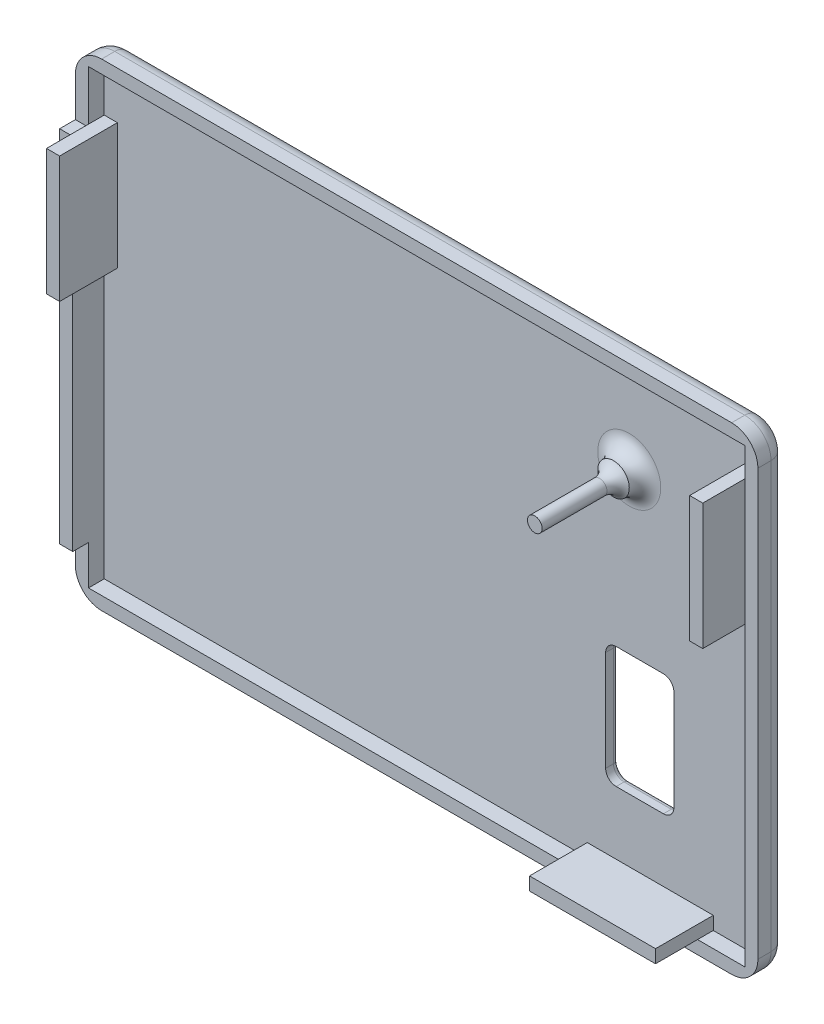
SolidWorks part; units mm, degrees
ref_plane "Front Plane" through (0, 0, 0) normal (0, 0, 1) x (1, 0, 0)
ref_plane "Top Plane" through (0, 0, 0) normal (0, 1, 0) x (1, 0, 0)
ref_plane "Right Plane" through (0, 0, 0) normal (1, 0, 0) x (0, 0, -1)
sketch "Sketch1" plane through (0, 0, 0) normal (0, 0, 1) x (1, 0, 0)
  line L1 (0, 0) -> (130, 0)
  line L2 (0, 0) -> (0, -91)
  line L3 (0, -91) -> (130, -91)
  line L4 (130, 0) -> (130, -91)
  dimension "D1" = 130
  dimension "D2" = 91
extrude "Boss-Extrude1" add sketch "Sketch1" along normal blind 2.5 contours L2 L1 L4 L3
sketch "Sketch2" plane through (0, 0, 2.5) normal (0, 0, 1) x (1, 0, 0)
  line L0 (0, 0) -> (130, 0) construction
  line L1 (0, 0) -> (130, 0)
  line L2 (0, 0) -> (0, -2.5)
  line L3 (0, -2.5) -> (130, -2.5)
  line L4 (130, 0) -> (130, -2.5)
  line L5 (0, 0) -> (0, -91) construction
  dimension "D1" = 2.5
  dimension "D2" = 130
sketch "Sketch3" plane through (0, 0, 2.5) normal (0, 0, 1) x (1, 0, 0)
  line L0 (0, -91) -> (130, -91) construction
  line L1 (0, -88.5) -> (130, -88.5)
  line L2 (0, -88.5) -> (0, -91)
  line L3 (0, -91) -> (130, -91)
  line L4 (130, -88.5) -> (130, -91)
  line L5 (130, 0) -> (130, -91) construction
  dimension "D1" = 130
  dimension "D2" = 2.5
sketch "Sketch4" plane through (0, 0, 2.5) normal (0, 0, 1) x (1, 0, 0)
  line L0 (0, -2.5) -> (130, -2.5) construction
  line L1 (127.5, -2.5) -> (130, -2.5)
  line L2 (127.5, -2.5) -> (127.5, -88.5)
  line L3 (127.5, -88.5) -> (130, -88.5)
  line L4 (130, -2.5) -> (130, -88.5)
  line L5 (0, -88.5) -> (130, -88.5) construction
  line L6 (130, 0) -> (130, -91) construction
  dimension "D1" = 2.5
sketch "Sketch5" plane through (0, 0, 2.5) normal (0, 0, 1) x (1, 0, 0)
  line L0 (0, 0) -> (0, -91) construction
  line L1 (0, -2.5) -> (2.5, -2.5)
  line L2 (0, -2.5) -> (0, -88.5)
  line L3 (0, -88.5) -> (2.5, -88.5)
  line L4 (2.5, -2.5) -> (2.5, -88.5)
  line L7 (0, -2.5) -> (130, -2.5) construction
  dimension "D1" = 2.5
  dimension "D2" = 86
extrude "Boss-Extrude2" add sketch "Sketch3" along normal blind 3
extrude "Boss-Extrude3" add sketch "Sketch2" along normal blind 3
extrude "Boss-Extrude4" add sketch "Sketch4" along normal blind 3
extrude "Boss-Extrude5" add sketch "Sketch5" along normal blind 3
fillet "Fillet2" radius 5 1 edges at (130, -91, 2.75)
fillet "Fillet3" radius 5 1 edges at (130, 0, 2.75)
fillet "Fillet4" radius 5 1 edges at (0, 0, 2.75)
fillet "Fillet5" radius 5 1 edges at (0, -91, 2.75)
sketch "Sketch7" plane through (0, 0, 5.5) normal (0, 0, 1) x (1, 0, 0)
  line L0 (0, -5) -> (0, -86) construction
  line L1 (0, -12.5) -> (2.5, -12.5)
  line L2 (0, -12.5) -> (0, -81)
  line L3 (0, -81) -> (2.5, -81)
  line L4 (2.5, -12.5) -> (2.5, -81)
  line L5 (2.5, -88.5) -> (2.5, -2.5) construction
  line L6 (127.5, -88.5) -> (2.5, -88.5) construction
  dimension "D1" = 68.5
  dimension "D2" = 7.5
extrude "Boss-Extrude6" add sketch "Sketch7" along normal blind 3
sketch "Sketch8" plane through (0, 0, 2.5) normal (0, 0, 1) x (1, 0, 0)
  line L0 (127.5, -88.5) -> (2.5, -88.5) construction
  line L1 (94.5, -86) -> (118.5, -86)
  line L2 (94.5, -86) -> (94.5, -88.5)
  line L3 (94.5, -88.5) -> (118.5, -88.5)
  line L4 (118.5, -86) -> (118.5, -88.5)
  line L5 (127.5, -2.5) -> (127.5, -88.5) construction
  dimension "D1" = 2.5
  dimension "D2" = 24
  dimension "D3" = 9
extrude "Boss-Extrude7" add sketch "Sketch8" along normal blind 11
sketch "Sketch9" plane through (0, 0, 2.5) normal (0, 0, 1) x (1, 0, 0)
  line L0 (127.5, -2.5) -> (127.5, -88.5) construction
  line L1 (125, -8) -> (127.5, -8)
  line L2 (125, -8) -> (125, -32)
  line L3 (125, -32) -> (127.5, -32)
  line L4 (127.5, -8) -> (127.5, -32)
  line L5 (2.5, -2.5) -> (127.5, -2.5) construction
  dimension "D1" = 5.5
  dimension "D2" = 24
  dimension "D3" = 2.5
extrude "Boss-Extrude8" add sketch "Sketch9" along normal blind 11
sketch "Sketch10" plane through (0, 0, 2.5) normal (0, 0, 1) x (1, 0, 0)
  line L0 (2.5, -88.5) -> (2.5, -2.5) construction
  line L1 (2.5, -12) -> (5, -12)
  line L2 (2.5, -12) -> (2.5, -36)
  line L3 (2.5, -36) -> (5, -36)
  line L4 (5, -12) -> (5, -36)
  line L5 (2.5, -2.5) -> (127.5, -2.5) construction
  dimension "D1" = 24
  dimension "D2" = 2.5
  dimension "D3" = 9.5
extrude "Boss-Extrude9" add sketch "Sketch10" along normal blind 11
sketch "Sketch11" plane through (0, 0, 2.5) normal (0, 0, 1) x (1, 0, 0)
  line L0 (94.5, -88.5) -> (2.5, -88.5) construction
  line L1 (2.5, -88.5) -> (2.5, -36) construction
  circle A0 centre (102.5, -20.5) radius 3
  dimension "D1" = 6
  dimension "D2" = 68
  dimension "D3" = 100
extrude "Boss-Extrude10" add sketch "Sketch11" along normal blind 3
sketch "Sketch12" plane through (0, 0, 5.5) normal (0, 0, 1) x (1, 0, 0)
  circle A0 centre (102.5, -20.5) radius 1.4
  circle A1 centre (102.5, -20.5) radius 3 construction
  dimension "D1" = 2.8
extrude "Boss-Extrude11" add sketch "Sketch12" along normal blind 15
sketch "Sketch13" plane through (0, 0, 2.5) normal (0, 0, 1) x (1, 0, 0)
  line L0 (130, -86) -> (130, -5) construction
  line L1 (98, -50.9) -> (111, -50.9)
  line L2 (98, -50.9) -> (98, -74)
  line L3 (98, -74) -> (111, -74)
  line L4 (111, -50.9) -> (111, -74)
  line L5 (5, -91) -> (125, -91) construction
  dimension "D1" = 13
  dimension "D2" = 23.1
  dimension "D3" = 19
  dimension "D4" = 17
extrude "Cut-Extrude1" cut sketch "Sketch13" against normal through all
fillet "Fillet17" radius 2 1 edges at (98, -74, 1.25)
fillet "Fillet18" radius 2 1 edges at (98, -50.9, 1.25)
fillet "Fillet19" radius 2 1 edges at (111, -50.9, 1.25)
fillet "Fillet20" radius 2 1 edges at (111, -74, 1.25)
fillet "Fillet23" radius 1 8 edges at (110.4142, -51.4858, 0) (111, -62.45, 0) (110.4142, -73.4142, 0) (104.5, -74, 0) (98.5858, -73.4142, 0) (98, -62.45, 0) (98.5858, -51.4858, 0) (104.5, -50.9, 0)
fillet "Fillet24" radius 3 8 edges at (1.4645, -89.5355, 0) (0, -45.5, 0) (1.4645, -1.4645, 0) (65, 0, 0) (128.5355, -1.4645, 0) (130, -45.5, 0) (128.5355, -89.5355, 0) (65, -91, 0)
fillet "Fillet25" radius 3 1 edges at (103.9, -20.5, 5.5)
fillet "Fillet26" radius 3 1 edges at (99.5, -20.5, 2.5)
